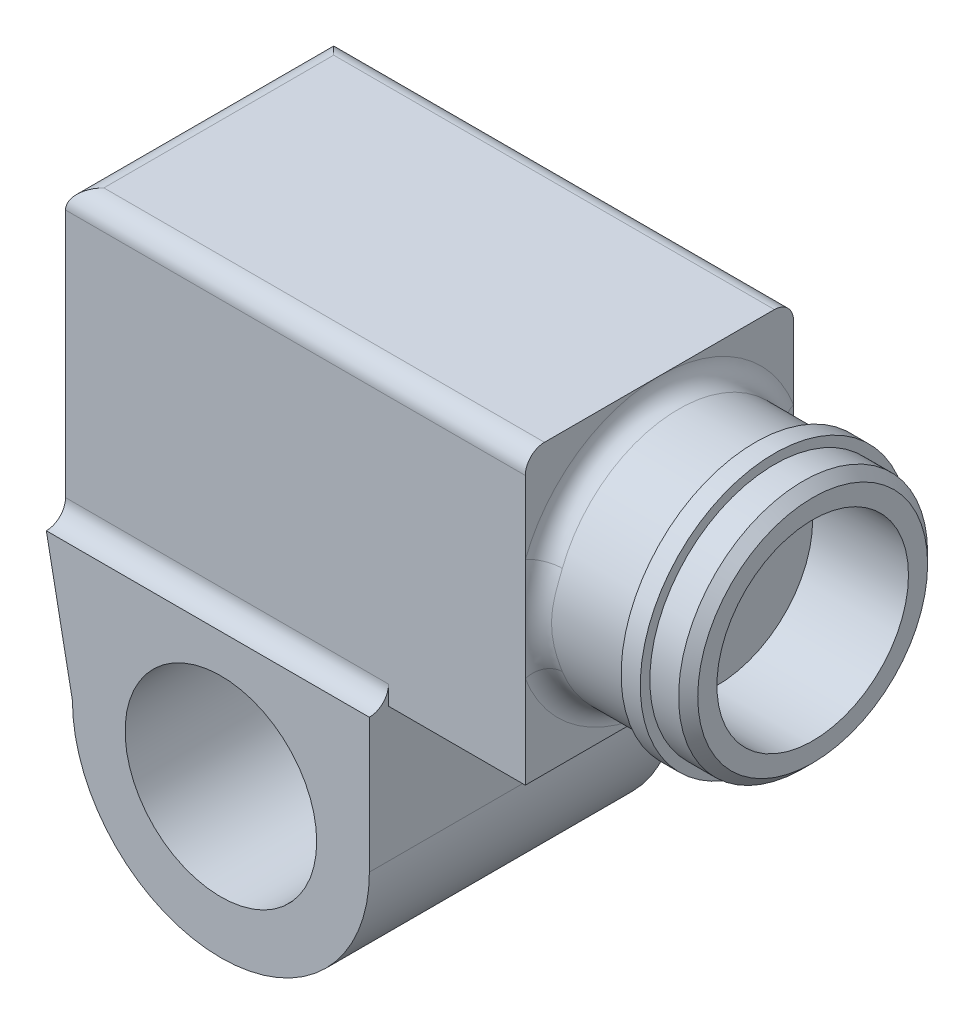
SolidWorks part; units mm, degrees
ref_plane "Front Plane" through (0, 0, 0) normal (0, 0, 1) x (1, 0, 0)
ref_plane "Top Plane" through (0, 0, 0) normal (0, 1, 0) x (1, 0, 0)
ref_plane "Right Plane" through (0, 0, 0) normal (1, 0, 0) x (0, 0, -1)
sketch "Sketch1" plane through (0, 0, 0) normal (0, 1, 0) x (1, 0, 0)
  line L1 (-120, -70) -> (120, -70)
  line L2 (-120, -70) -> (-120, 70)
  line L3 (-120, 70) -> (120, 70)
  line L4 (120, -70) -> (120, 70)
  line L5 (-120, -70) -> (120, 70) construction
  line L6 (-120, 70) -> (120, -70) construction
  point P0 (0, 0)
  dimension "D1" = 140
  dimension "D2" = 240
extrude "Boss-Extrude1" add sketch "Sketch1" along normal blind 150
sketch "Sketch2" plane through (120, 0, 0) normal (1, 0, 0) x (0, 0, -1)
  line L0 (-70, 0) -> (70, 150) construction
  circle A0 centre (0, 75) radius 65
  dimension "D1" = 130
extrude "Boss-Extrude2" add sketch "Sketch2" along normal blind 50 contours A0
sketch "Sketch3" plane through (170, 0, 0) normal (1, 0, 0) x (0, 0, -1)
  circle A0 centre (0, 75) radius 70
  dimension "D1" = 140
extrude "Boss-Extrude3" add sketch "Sketch3" along normal blind 10
sketch "Sketch4" plane through (0, 0, 0) normal (0, 0, 1) x (1, 0, 0)
  line L0 (-28.8934, 0) -> (-28.8934, -70) construction
  line L1 (-120, 0) -> (120, 0) construction
  line L2 (48.6066, -70) -> (48.6066, 0)
  line L3 (-120, 0) -> (-106.3934, -70)
  line L4 (-120, 0) -> (48.6066, 0)
  line L5 (-120, 150) -> (-120, 0) construction
  circle A0 centre (-28.8934, -70) radius 50
  arc A1 (-106.3934, -70) -> (48.6066, -70) centre (-28.8934, -70) ccw
  point P5 (-28.4972, 2.0232)
  point P10 (-120, 0)
  point P13 (-110.9891, 0)
  point P14 (0, 0)
  dimension "D1" = 155
  dimension "D2" = 100
  dimension "D3" = 70
  dimension "D4" = 191
extrude "Boss-Extrude4" add sketch "Sketch4" along normal mid plane 160
fillet "Fillet1" radius 10 3 edges at (-35.6967, 0, -70) (120, 75, -65) (-35.6967, 0, 70)
sketch "Sketch7" plane through (180, 0, 0) normal (1, 0, 0) x (0, 0, -1)
  circle A0 centre (0, 75) radius 65
  dimension "D1" = 130
extrude "Boss-Extrude5" add sketch "Sketch7" along normal blind 20
fillet "Fillet2" radius 10 3 edges at (-120, 150, 0) (0, 150, -70) (0, 150, 70)
sketch "Sketch8" plane through (200, 0, 0) normal (1, 0, 0) x (0, 0, -1)
  circle A0 centre (0, 75) radius 50
  dimension "D1" = 100
extrude "Cut-Extrude1" cut sketch "Sketch8" against normal blind 50
chamfer "Chamfer1" distance 5 angle 45 1 edges at (200, 75, -65)
